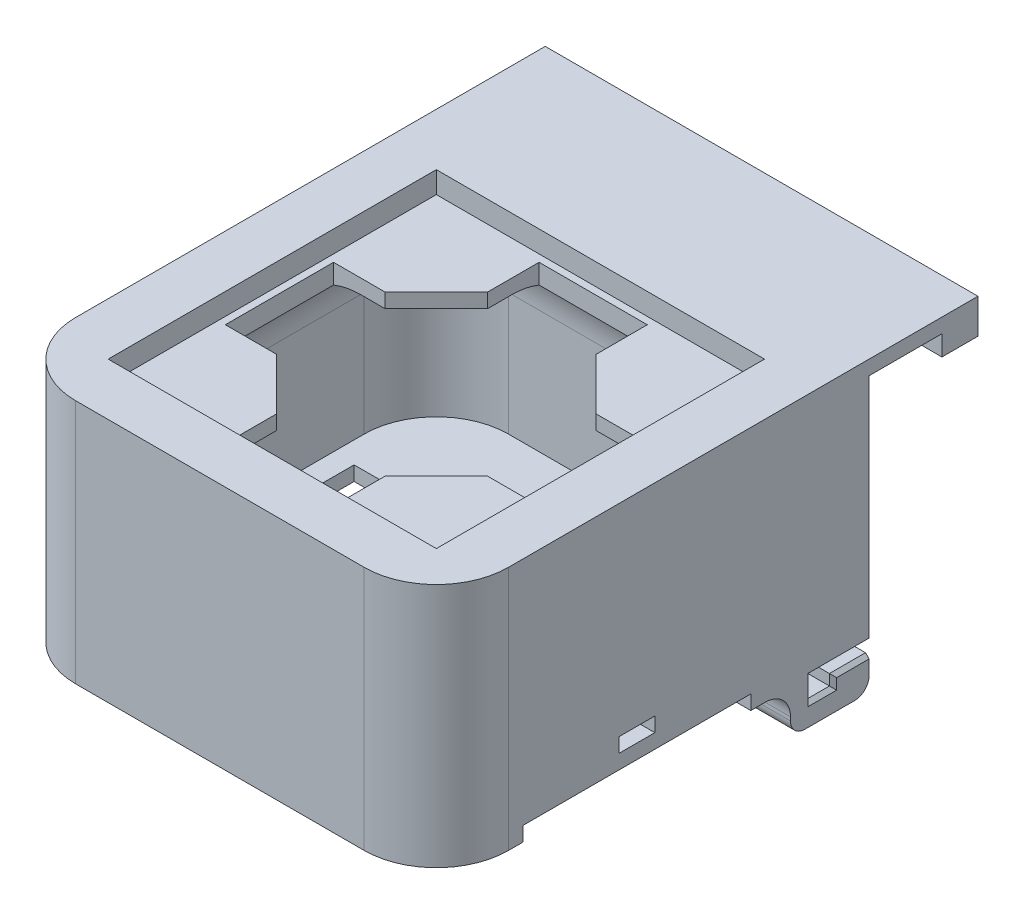
SolidWorks part; units mm, degrees
ref_plane "Plan de face" through (0, 0, 0) normal (0, 0, 1) x (1, 0, 0)
ref_plane "Plan de dessus" through (0, 0, 0) normal (0, 1, 0) x (1, 0, 0)
ref_plane "Plan de droite" through (0, 0, 0) normal (1, 0, 0) x (0, 0, -1)
sketch "Esquisse1" plane through (0, 0, 0) normal (1, 0, 0) x (0, 0, -1)
  line L4 (0, 0) -> (-8, 0)
  line L5 (-60, 0) -> (-60, 34)
  line L6 (-60, 34) -> (15.1, 34)
  line L7 (15.1, 34) -> (15.1, 29.2)
  line L8 (10.1, 29.2) -> (10.1, 32)
  line L9 (10.1, 32) -> (0, 32)
  line L11 (10.1, 29.2) -> (15.1, 29.2)
  line L14 (0, 0) -> (0, 32)
  line L15 (-8, 0) -> (-8, -3)
  line L16 (-8, -3) -> (-5, -3)
  line L17 (-5, -3) -> (-5, -1.5)
  line L18 (-5, -1.5) -> (0, -1.5)
  line L19 (0, -1.5) -> (0, -4)
  line L20 (-2, -6) -> (-8.9, -6)
  line L21 (-10.9, -4) -> (-10.9, -3.5)
  line L22 (-14.4, 0) -> (-60, 0)
  arc A0 (-10.9, -3.5) -> (-14.4, 0) centre (-14.4, -3.5) ccw
  arc A1 (-8.9, -6) -> (-10.9, -4) centre (-8.9, -4) cw
  arc A2 (0, -4) -> (-2, -6) centre (-2, -4) cw
  point P5 (-10.9, 0)
  dimension "D6" = 3.5
  dimension "D12" = 2
  dimension "D2" = 10.1
  dimension "D3" = 5
  dimension "D4" = 2
  dimension "D5" = 34
  dimension "D7" = 60
  dimension "D8" = 2.9
  dimension "D11" = 2.8
  dimension "D14" = 3
  dimension "D15" = 1.5
  dimension "D16" = 3
  dimension "D17" = 5
  dimension "D18" = 3
extrude "Boss.-Extru.1" add sketch "Esquisse1" along normal blind 60
sketch "Esquisse4" plane through (0, 34, 0) normal (0, 1, 0) x (1, 0, 0)
  line L0 (7.25, -7.25) -> (52.75, -52.75) construction
  line L1 (7.25, -52.75) -> (52.75, -52.75)
  line L2 (7.25, -52.75) -> (7.25, -7.25)
  line L3 (7.25, -7.25) -> (52.75, -7.25)
  line L4 (52.75, -52.75) -> (52.75, -7.25)
  line L5 (30, -60) -> (30, -30) construction
  line L6 (60, -60) -> (0, -60) construction
  line L7 (30, -30) -> (0, -30) construction
  line L8 (0, 15.1) -> (0, -60) construction
  dimension "D1" = 45.5
extrude "Enlèv. mat.-Extru.2" cut sketch "Esquisse4" against normal blind 3
sketch "Esquisse6" plane through (0, 31, 0) normal (0, 1, 0) x (1, 0, 0)
  line L0 (8.25, -22.5) -> (15.375, -22.5)
  line L2 (15.375, -22.5) -> (22.5, -15.375)
  line L3 (22.5, -15.375) -> (22.5, -8.25)
  line L5 (22.5, -8.25) -> (37.5, -8.25)
  line L6 (37.5, -8.25) -> (37.5, -15.375)
  line L7 (37.5, -15.375) -> (44.625, -22.5)
  line L8 (44.625, -22.5) -> (51.75, -22.5)
  line L10 (51.75, -22.5) -> (51.75, -37.5)
  line L11 (51.75, -37.5) -> (44.625, -37.5)
  line L12 (44.625, -37.5) -> (37.5, -44.625)
  line L13 (37.5, -44.625) -> (37.5, -51.75)
  line L15 (37.5, -51.75) -> (22.5, -51.75)
  line L16 (22.5, -51.75) -> (22.5, -44.625)
  line L17 (22.5, -44.625) -> (15.375, -37.5)
  line L18 (15.375, -37.5) -> (8.25, -37.5)
  line L20 (8.25, -37.5) -> (8.25, -22.5)
  line L21 (7.25, -52.75) -> (52.75, -52.75) construction
  line L22 (52.75, -7.25) -> (7.25, -7.25) construction
  line L23 (7.25, -7.25) -> (7.25, -52.75) construction
  line L24 (52.75, -52.75) -> (52.75, -7.25) construction
  dimension "D1" = 45
  dimension "D2" = 15
  dimension "D3" = 1
  dimension "D4" = 1
  dimension "D5" = 1
  dimension "D6" = 1
  dimension "D7" = 7.125
extrude "Enlèv. mat.-Extru.4" cut sketch "Esquisse6" against normal blind 2
sketch "Esquisse5" plane through (0, 0, 0) normal (0, -1, 0) x (1, 0, 0)
  line L0 (60, 8) -> (60, 0) construction
  line L1 (2, 58) -> (58, 58)
  line L2 (2, 58) -> (2, 2)
  line L3 (2, 2) -> (58, 2)
  line L4 (58, 58) -> (58, 2)
  line L5 (60, 60) -> (0, 60) construction
  line L6 (0, 8) -> (0, 0) construction
  line L8 (60, 0) -> (0, 0) construction
  dimension "D1" = 2
  dimension "D2" = 2
  dimension "D3" = 2
  dimension "D4" = 2
extrude "Enlèv. mat.-Extru.3" cut sketch "Esquisse5" against normal up to surface (29 mm away) from offset 2 up to face at (30, 29, 30) offset against normal yes
sketch "Esquisse7" plane through (0, 0, 0) normal (0, -1, 0) x (1, 0, 0)
  line L0 (60, 60) -> (0, 60) construction
  line L1 (17.5, 30) -> (0, 30) construction
  line L3 (0, 60) -> (0, 14.4) construction
  line L4 (17.5, 30) -> (42.5, 30) construction
  line L5 (42.5, 30) -> (60, 30) construction
  line L6 (60, 60) -> (60, 14.4) construction
  circle A0 centre (17.5, 30) radius 6
  circle A1 centre (42.5, 30) radius 6
  dimension "D1" = 12
  dimension "D2" = 30
  dimension "D3" = 25
extrude "Enlèv. mat.-Extru.5" [suppressed] cut sketch "Esquisse7" against normal blind 5
fillet "Congé1" radius 10 10 edges at (30, 29, 2) (58, 29, 30) (30, 29, 58) (2, 29, 30) (58, 15.5, 58) (58, 15.5, 2) (2, 15.5, 2) (2, 15.5, 58) (60, 17, 60) (0, 17, 60)
chamfer "Chanfrein1" distance 0.5 angle 45 5 edges at (60, -1.5, 2.5) (60, -2.25, 5) (60, -3, 6.5) (60, -1.5, 8) (60, 0, 4)
ref_plane "Plan1" through (30, 0, 0) normal (1, 0, 0) x (0, 0, -1)
sketch "Esquisse15" plane through (60, 0, 0) normal (1, 0, 0) x (0, 0, -1)
  line L0 (-48, 0) -> (-48, 2)
  line L1 (-50, 0) -> (-14.4, 0) construction
  line L2 (-48, 2) -> (-16.4, 2)
  line L7 (-16.4, 2) -> (-16.4, 0)
  line L9 (-48, 0) -> (-16.4, 0)
  line L11 (-32.2, 4) -> (-32.2, 2) construction
  line L12 (-34.7, 6) -> (-29.7, 6)
  line L13 (-34.7, 6) -> (-34.7, 4)
  line L14 (-34.7, 4) -> (-29.7, 4)
  line L15 (-29.7, 6) -> (-29.7, 4)
  arc A0 (-10.9, -3.5) -> (-14.4, 0) centre (-14.4, -3.5) ccw construction
  dimension "D1" = 2
  dimension "D2" = 2
  dimension "D3" = 31.6
  dimension "D4" = 2
  dimension "D5" = 5
  dimension "D6" = 2
extrude "Enlèv. mat.-Extru.11" cut sketch "Esquisse15" against normal blind 55
